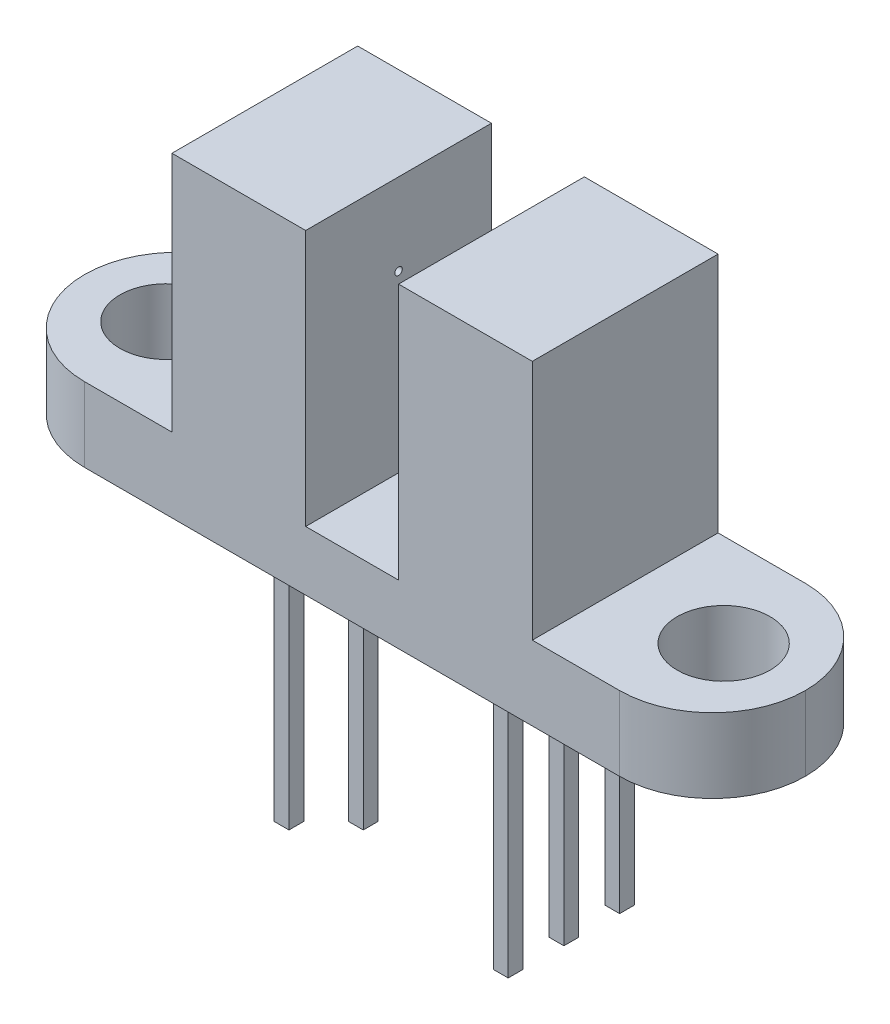
SolidWorks part; units mm, degrees
ref_plane "Front" through (0, 0, 0) normal (0, 0, 1) x (1, 0, 0)
ref_plane "Top" through (0, 0, 0) normal (0, 1, 0) x (1, 0, 0)
ref_plane "Right" through (0, 0, 0) normal (1, 0, 0) x (0, 0, -1)
sketch "Sketch1" plane through (0, 0, 0) normal (0, 0, 1) x (1, 0, 0)
  line L0 (12.319, 0) -> (-12.319, 0)
  line L1 (-12.319, 0) -> (-12.319, 2.54)
  line L2 (-12.319, 2.54) -> (-6.1595, 2.54)
  line L3 (-6.1595, 2.54) -> (-6.1595, 10.795)
  line L4 (-6.1595, 10.795) -> (-1.5875, 10.795)
  line L5 (-1.5875, 10.795) -> (-1.5875, 2.032)
  line L6 (-1.5875, 2.032) -> (1.5875, 2.032)
  line L7 (1.5875, 2.032) -> (1.5875, 10.795)
  line L8 (1.5875, 10.795) -> (6.1595, 10.795)
  line L9 (6.1595, 10.795) -> (6.1595, 2.54)
  line L10 (6.1595, 2.54) -> (12.319, 2.54)
  line L11 (12.319, 2.54) -> (12.319, 0)
  point P14 (0, 2.032)
  dimension "D1" = 24.638
  dimension "D2" = 2.54
  dimension "D3" = 12.319
  dimension "D4" = 8.763
  dimension "D5" = 3.175
  dimension "D6" = 10.795
extrude "Boss-Extrude1" add sketch "Sketch1" along normal mid plane 6.35
fillet "Fillet1" radius 3.175 4 edges at (-12.319, 1.27, 3.175) (-12.319, 1.27, -3.175) (12.319, 1.27, -3.175) (12.319, 1.27, 3.175)
sketch "Sketch2" plane through (0, 2.54, 0) normal (0, 1, 0) x (1, 0, 0)
  circle A0 centre (-9.525, 0) radius 1.5875
  circle A1 centre (9.525, 0) radius 1.5875
  dimension "D1" = 19.05
  dimension "D2" = 3.175
  dimension "D3" = 9.525
extrude "Cut-Extrude1" cut sketch "Sketch2" against normal through all
sketch "Sketch3" plane through (1.5875, 0, 0) normal (-1, 0, 0) x (0, 0, 1)
  line L0 (3.175, 10.795) -> (-3.175, 10.795) construction
  circle A0 centre (0, 8.001) radius 0.127
  dimension "D1" = 2.794
  dimension "D2" = 0.254
extrude "Cut-Extrude2" cut sketch "Sketch3" against normal blind 0.254
sketch "Sketch4" plane through (-1.5875, 0, 0) normal (1, 0, 0) x (0, 0, -1)
  circle A0 centre (0, 8.001) radius 0.127 construction
  circle A1 centre (0, 8.001) radius 0.127
extrude "Cut-Extrude3" cut sketch "Sketch4" against normal blind 0.254
sketch "Sketch5" plane through (0, 0, 0) normal (0, -1, 0) x (1, 0, 0)
  line L0 (-3.81, 1.524) -> (-4.318, 1.016) construction
  line L1 (-4.318, 1.524) -> (-3.81, 1.524)
  line L2 (-4.318, 1.524) -> (-4.318, 1.016)
  line L3 (-4.318, 1.016) -> (-3.81, 1.016)
  line L4 (-3.81, 1.524) -> (-3.81, 1.016)
  line L5 (-4.318, -1.016) -> (-3.81, -1.016)
  line L6 (-4.318, -1.016) -> (-4.318, -1.524)
  line L7 (-4.318, -1.524) -> (-3.81, -1.524)
  line L8 (-3.81, -1.016) -> (-3.81, -1.524)
  line L9 (3.81, 2.159) -> (4.318, 2.159)
  line L10 (3.81, 2.159) -> (3.81, 1.651)
  line L11 (3.81, 1.651) -> (4.318, 1.651)
  line L12 (4.318, 2.159) -> (4.318, 1.651)
  line L13 (3.81, 0.254) -> (4.318, 0.254)
  line L14 (3.81, 0.254) -> (3.81, -0.254)
  line L15 (3.81, -0.254) -> (4.318, -0.254)
  line L16 (4.318, 0.254) -> (4.318, -0.254)
  line L17 (3.81, -1.651) -> (4.318, -1.651)
  line L18 (3.81, -1.651) -> (3.81, -2.159)
  line L19 (3.81, -2.159) -> (4.318, -2.159)
  line L20 (4.318, -1.651) -> (4.318, -2.159)
  line L21 (-3.81, -1.016) -> (-4.318, -1.524) construction
  point P20 (-4.318, 1.27)
  point P21 (-4.318, -1.27)
  point P22 (4.318, 1.905)
  point P23 (4.318, 0)
  point P24 (4.318, -1.905)
  point P25 (-4.064, 1.524)
  point P26 (4.064, 2.159)
  point P28 (3.81, 0)
  dimension "D1" = 0.508
  dimension "D2" = 0.508
  dimension "D3" = 2.54
  dimension "D4" = 1.905
  dimension "D5" = 3.81
  dimension "D6" = 8.128
  dimension "D7" = 4.064
  dimension "D8" = 1.27
extrude "Boss-Extrude2" add sketch "Sketch5" along normal blind 8.89
sketch "Sketch6" plane through (0, -8.89, 0) normal (0, -1, 0) x (1, 0, 0)
  line L4 (-4.318, -1.016) -> (-4.318, -1.524)
  line L5 (-4.318, -1.524) -> (-3.81, -1.524)
  line L6 (-3.81, -1.524) -> (-3.81, -1.016)
  line L7 (-3.81, -1.016) -> (-4.318, -1.016)
  line L8 (-4.318, -1.016) -> (-4.318, -1.524)
  line L9 (-4.318, -1.524) -> (-3.81, -1.524)
  line L10 (-3.81, -1.524) -> (-3.81, -1.016)
  line L11 (-3.81, -1.016) -> (-4.318, -1.016)
  dimension "D1" = 0
extrude "Boss-Extrude3" add sketch "Sketch6" along normal blind 1.27
